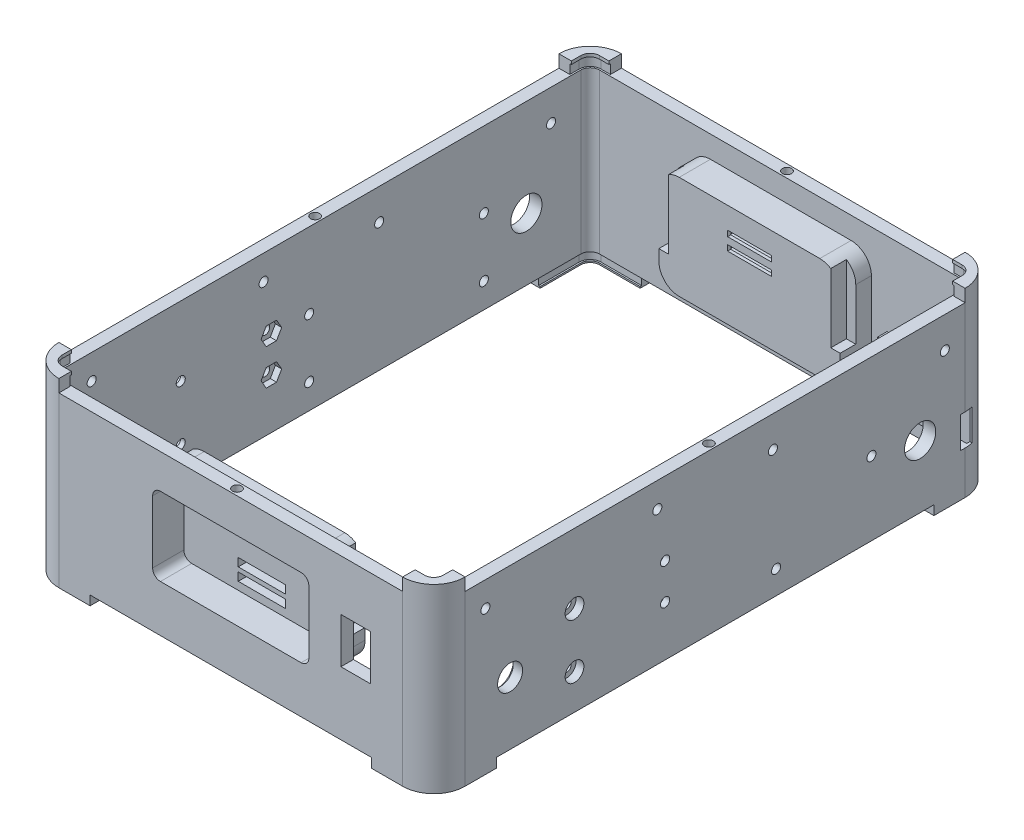
SolidWorks part; units mm, degrees
ref_plane "Спереди" through (0, 0, 0) normal (0, 0, 1) x (1, 0, 0)
ref_plane "Сверху" through (0, 0, 0) normal (0, 1, 0) x (1, 0, 0)
ref_plane "Справа" through (0, 0, 0) normal (1, 0, 0) x (0, 0, -1)
sketch "Эскиз1" plane through (0, 0, 0) normal (0, 1, 0) x (1, 0, 0)
  line L1 (-65, -90) -> (65, -90)
  line L2 (-65, -90) -> (-65, 90)
  line L3 (-65, 90) -> (65, 90)
  line L4 (65, -90) -> (65, 90)
  line L5 (-65, -90) -> (65, 90) construction
  line L6 (-65, 90) -> (65, -90) construction
  point P0 (0, 0)
  dimension "D1" = 130
  dimension "D2" = 180
extrude "Бобышка-Вытянуть1" add sketch "Эскиз1" along normal blind 55
sketch "Эскиз2" plane through (0, 0, 90) normal (0, 0, 1) x (1, 0, 0)
  line L0 (-1050, 27.5) -> (48950, 27.5) construction
  line L1 (-65, 55) -> (-65, 0) construction
  line L2 (0, -999.2777) -> (0, 49000.7223) construction
  line L4 (-22.5, 15) -> (22.5, 15)
  line L5 (-25, 17.5) -> (-25, 37.5)
  line L6 (-22.5, 40) -> (22.5, 40)
  line L7 (25, 17.5) -> (25, 37.5)
  line L8 (-25, 15) -> (25, 40) construction
  line L9 (-25, 40) -> (25, 15) construction
  arc A0 (-22.5, 40) -> (-25, 37.5) centre (-22.5, 37.5) ccw
  arc A1 (-25, 17.5) -> (-22.5, 15) centre (-22.5, 17.5) ccw
  arc A2 (25, 17.5) -> (22.5, 15) centre (22.5, 17.5) cw
  arc A3 (25, 37.5) -> (22.5, 40) centre (22.5, 37.5) ccw
  point P5 (-65, 27.5)
  point P6 (0, 27.5)
  dimension "D3" = 2.5
  dimension "D4" = 2.5
  dimension "D1" = 25
  dimension "D2" = 50
extrude "Вырез-Вытянуть1" cut sketch "Эскиз2" against normal blind 10
sketch "Эскиз4" plane through (0, 55, 0) normal (0, 1, 0) x (1, 0, 0)
  line L0 (0, -1000) -> (0, 49000) construction
  line L1 (-1000, 0) -> (49000, 0) construction
  line L2 (-22.5, 41.5) -> (22.5, 41.5)
  line L3 (-25, 44) -> (-25, 64)
  line L4 (-22.5, 66.5) -> (22.5, 66.5)
  line L5 (-22.5, -12.5) -> (22.5, -12.5)
  line L6 (-25, -10) -> (-25, 10)
  line L7 (-22.5, 12.5) -> (22.5, 12.5)
  line L8 (25, -10) -> (25, 10)
  line L9 (-25, -12.5) -> (25, 12.5) construction
  line L10 (-25, 12.5) -> (25, -12.5) construction
  line L11 (25, 44) -> (25, 64)
  line L12 (-25, 41.5) -> (25, 66.5) construction
  line L13 (-25, 66.5) -> (25, 41.5) construction
  line L14 (-25, -12.5) -> (25, -12.5) [skipped]
  line L15 (-25, -12.5) -> (-25, 12.5) [skipped]
  line L16 (-25, 12.5) -> (25, 12.5) [skipped]
  line L17 (25, -12.5) -> (25, 12.5) [skipped]
  line L18 (-25, -12.5) -> (25, 12.5) construction
  line L19 (-25, 12.5) -> (25, -12.5) construction
  line L20 (-22.5, -66.5) -> (22.5, -66.5)
  line L21 (-25, -64) -> (-25, -44)
  line L22 (-22.5, -41.5) -> (22.5, -41.5)
  line L23 (25, -64) -> (25, -44)
  line L24 (-25, -66.5) -> (25, -41.5) construction
  line L25 (-25, -41.5) -> (25, -66.5) construction
  arc A0 (22.5, -41.5) -> (25, -44) centre (22.5, -44) cw
  arc A1 (25, -64) -> (22.5, -66.5) centre (22.5, -64) cw
  arc A2 (-22.5, -66.5) -> (-25, -64) centre (-22.5, -64) cw
  arc A3 (-25, -44) -> (-22.5, -41.5) centre (-22.5, -44) cw
  arc A4 (-25, 64) -> (-22.5, 66.5) centre (-22.5, 64) cw
  arc A5 (-22.5, 12.5) -> (-25, 10) centre (-22.5, 10) ccw
  arc A6 (25, -10) -> (22.5, -12.5) centre (22.5, -10) cw
  arc A7 (22.5, 66.5) -> (25, 64) centre (22.5, 64) cw
  arc A8 (25, 44) -> (22.5, 41.5) centre (22.5, 44) cw
  arc A9 (-22.5, 41.5) -> (-25, 44) centre (-22.5, 44) cw
  arc A10 (22.5, 12.5) -> (25, 10) centre (22.5, 10) cw
  arc A11 (-22.5, -12.5) -> (-25, -10) centre (-22.5, -10) cw
  point P8 (0, 0)
  point P9 (0, 54)
  point P18 (0, 0)
  point P23 (0, -54)
  dimension "D7" = 2.5
  dimension "D8" = 2.5
  dimension "D1" = 25
  dimension "D2" = 50
  dimension "D5" = 41.5
  dimension "D6" = 41.5
  dimension "D3" = 2
  dimension "D4" = 2
extrude "Вырез-Вытянуть2" cut sketch "Эскиз4" against normal blind 10
mirror "Зеркальное отражение1" about plane through (0, 0, 0) normal (0, 0, 1) of "Вырез-Вытянуть1"
shell "Оболочка1" thickness 4 removed face at (0, 0, 0)
sketch "Эскиз5" plane through (-65, 0, 0) normal (-1, 0, 0) x (0, 0, 1)
  line L0 (45, 28.75) -> (45, 11.25) construction
  line L2 (90, 55) -> (90, 0) construction
  line L4 (-90, 0) -> (90, 0) construction
  line L7 (-1075, 20) -> (48925, 20) construction
  line L8 (-90, 55) -> (-90, 0) construction
  circle A3 centre (45, 28.75) radius 1.45
  circle A4 centre (45, 11.25) radius 1.45
  circle A5 centre (65.6, 20) radius 4
  circle A6 centre (-65.6, 20) radius 5
  dimension "D2" = 17.5
  dimension "D3" = 20
  dimension "D6" = 10
  dimension "D1" = 17.5
  dimension "D5" = 2.9
  dimension "D9" = 45
  dimension "D10" = 20.6
  dimension "D11" = 8
  dimension "D4" = 24.4
extrude "Вырез-Вытянуть3" cut sketch "Эскиз5" against normal blind 15
sketch "Эскиз6" plane through (-65, 0, 0) normal (-1, 0, 0) x (0, 0, 1)
  circle A2 centre (45, 28.75) radius 3
  circle A3 centre (45, 11.25) radius 3
  dimension "D1" = 6
extrude "Вырез-Вытянуть4" cut sketch "Эскиз6" against normal blind 2.5
sketch "Эскиз11" plane through (-61, 0, 0) normal (1, 0, 0) x (0, 0, -1)
  circle A1 centre (-65.6, 20) radius 5
  dimension "D1" = 10
extrude "Вырез-Вытянуть16" cut sketch "Эскиз11" against normal blind 1
mirror "Зеркальное отражение2" about plane through (0, 0, 0) normal (1, 0, 0) of "Вырез-Вытянуть3", "Вырез-Вытянуть4", "Вырез-Вытянуть16"
sketch "Эскиз12" plane through (0, 11, 0) normal (0, -1, 0) x (-1, 0, 0)
  line L0 (-1014.7864, -78) -> (48985.2136, -78) construction
  line L1 (22.5, -76) -> (-22.5, -76) construction
  line L2 (0, -1061) -> (0, 48939) construction
  line L3 (-10, -1061) -> (-10, 48939) construction
  line L4 (10, -1061) -> (10, 48939) construction
  circle A0 centre (-10, -78) radius 1.45
  circle A1 centre (10, -78) radius 1.45
  point P7 (0, -76)
  dimension "D4" = 2.9
  dimension "D1" = 2
  dimension "D2" = 20
  dimension "D3" = 10
extrude "Вырез-Вытянуть17" cut sketch "Эскиз12" against normal blind 14
sketch "Эскиз15" plane through (0, 45, 0) normal (0, 1, 0) x (1, 0, 0)
  line L0 (-1010.1672, -62.5) -> (48989.8328, -62.5) construction
  line L1 (0, -1031.5) -> (0, 48968.5) construction
  line L2 (-7.6, -63.8) -> (7.6, -63.8)
  line L3 (-7.6, -63.8) -> (-7.6, -61.2)
  line L4 (-7.6, -61.2) -> (7.6, -61.2)
  line L5 (7.6, -63.8) -> (7.6, -61.2)
  line L6 (-7.6, -63.8) -> (7.6, -61.2) construction
  line L7 (-7.6, -61.2) -> (7.6, -63.8) construction
  line L8 (22.5, -41.5) -> (-22.5, -41.5) construction
  line L9 (-22.5, -66.5) -> (22.5, -66.5) construction
  line L10 (-7.6, -9.8) -> (7.6, -9.8)
  line L11 (-7.6, -9.8) -> (-7.6, -7.2)
  line L12 (-7.6, -7.2) -> (7.6, -7.2)
  line L13 (7.6, -9.8) -> (7.6, -7.2)
  line L14 (-7.6, -9.8) -> (7.6, -7.2) construction
  line L15 (-7.6, -7.2) -> (7.6, -9.8) construction
  line L16 (-7.6, 44.2) -> (7.6, 44.2)
  line L17 (-7.6, 44.2) -> (-7.6, 46.8)
  line L18 (-7.6, 46.8) -> (7.6, 46.8)
  line L19 (7.6, 44.2) -> (7.6, 46.8)
  line L20 (-7.6, 44.2) -> (7.6, 46.8) construction
  line L21 (-7.6, 46.8) -> (7.6, 44.2) construction
  line L23 (22.5, 12.5) -> (-22.5, 12.5) construction
  line L24 (-7.6, -59.8) -> (7.6, -59.8)
  line L25 (-7.6, -59.8) -> (-7.6, -57.2)
  line L26 (-7.6, -57.2) -> (7.6, -57.2)
  line L27 (7.6, -59.8) -> (7.6, -57.2)
  line L28 (-7.6, -59.8) -> (7.6, -57.2) construction
  line L29 (-7.6, -57.2) -> (7.6, -59.8) construction
  line L30 (-7.6, -5.8) -> (7.6, -5.8)
  line L31 (-7.6, -5.8) -> (-7.6, -3.2)
  line L32 (-7.6, -3.2) -> (7.6, -3.2)
  line L33 (7.6, -5.8) -> (7.6, -3.2)
  line L34 (-7.6, -5.8) -> (7.6, -3.2) construction
  line L35 (-7.6, -3.2) -> (7.6, -5.8) construction
  line L36 (-7.6, 48.2) -> (7.6, 48.2)
  line L37 (-7.6, 48.2) -> (-7.6, 50.8)
  line L38 (-7.6, 50.8) -> (7.6, 50.8)
  line L39 (7.6, 48.2) -> (7.6, 50.8)
  line L40 (-7.6, 48.2) -> (7.6, 50.8) construction
  line L41 (-7.6, 50.8) -> (7.6, 48.2) construction
  line L42 (-22.5, -12.5) -> (22.5, -12.5) construction
  circle A0 centre (-20, -46.5) radius 2.5
  circle A1 centre (20, -46.5) radius 2.5
  circle A2 centre (-20, 7.5) radius 2.5
  circle A3 centre (20, 7.5) radius 2.5
  circle A4 centre (-20, 61.5) radius 2.5
  circle A5 centre (20, 61.5) radius 2.5
  point P1 (0, -62.5)
  point P12 (0, -41.5)
  point P16 (0, -8.5)
  point P21 (0, 45.5)
  point P41 (0, -4.5)
  point P42 (0, -58.5)
  point P51 (0, 49.5)
  dimension "D6" = 40
  dimension "D8" = 5
  dimension "D1" = 2.6
  dimension "D2" = 15.2
  dimension "D3" = 4
  dimension "D4" = 3
  dimension "D5" = 4
  dimension "D7" = 40
  dimension "D9" = 5
  dimension "D10" = 3
  dimension "D11" = 5
  dimension "D13" = 4
  dimension "D15" = 4
  dimension "D12" = 2
  dimension "D14" = 3
extrude "Вырез-Вытянуть20" cut sketch "Эскиз15" against normal blind 3
sketch "Эскиз16" plane through (0, 42, 0) normal (0, 1, 0) x (1, 0, 0)
  line L0 (-7.6, -62.5) -> (7.6, -62.5) construction
  line L1 (-7.6, -61.2) -> (-7.6, -63.8) construction
  line L2 (7.6, -63.8) -> (7.6, -61.2) construction
  line L3 (0, -1000) -> (0, 49000) construction
  line L4 (-7, -63.4) -> (7, -63.4)
  line L5 (-7, -63.4) -> (-7, -61.6)
  line L6 (-7, -61.6) -> (7, -61.6)
  line L7 (7, -63.4) -> (7, -61.6)
  line L8 (-7, -63.4) -> (7, -61.6) construction
  line L9 (-7, -61.6) -> (7, -63.4) construction
  line L10 (-7, -9.4) -> (7, -9.4)
  line L11 (-7, -9.4) -> (-7, -7.6)
  line L12 (-7, -7.6) -> (7, -7.6)
  line L13 (7, -9.4) -> (7, -7.6)
  line L14 (-7.6, -8.5) -> (7.6, -8.5) construction
  line L15 (-7, -9.4) -> (7, -7.6) construction
  line L16 (-7, -7.6) -> (7, -9.4) construction
  line L17 (-7, 44.6) -> (7, 44.6)
  line L18 (-7, 44.6) -> (-7, 46.4)
  line L19 (-7, 46.4) -> (7, 46.4)
  line L20 (7, 44.6) -> (7, 46.4)
  line L21 (-7.6, 45.5) -> (7.6, 45.5) construction
  line L22 (-7, 44.6) -> (7, 46.4) construction
  line L23 (-7, 46.4) -> (7, 44.6) construction
  line L24 (-7.6, -7.2) -> (-7.6, -9.8) construction
  line L25 (-7.6, -58.5) -> (7.6, -58.5) construction
  line L26 (-7, -59.4) -> (7, -59.4)
  line L27 (-7, -59.4) -> (-7, -57.6)
  line L28 (-7, -57.6) -> (7, -57.6)
  line L29 (7, -59.4) -> (7, -57.6)
  line L30 (-7, -59.4) -> (7, -57.6) construction
  line L31 (-7, -57.6) -> (7, -59.4) construction
  line L32 (-7.6, -57.2) -> (-7.6, -59.8) construction
  line L33 (7.6, -59.8) -> (7.6, -57.2) construction
  line L34 (-7.6, -4.5) -> (7.6, -4.5) construction
  line L35 (-7.6, -3.2) -> (-7.6, -5.8) construction
  line L36 (7.6, -5.8) -> (7.6, -3.2) construction
  line L37 (-7.6, -9.8) -> (7.6, -9.8) construction
  line L38 (-7, -5.4) -> (7, -5.4)
  line L39 (-7, -5.4) -> (-7, -3.6)
  line L40 (-7, -3.6) -> (7, -3.6)
  line L41 (7, -5.4) -> (7, -3.6)
  line L42 (-7, -5.4) -> (7, -3.6) construction
  line L43 (-7, -3.6) -> (7, -5.4) construction
  line L44 (7.6, -9.8) -> (7.6, -7.2) construction
  line L45 (-7.6, 46.8) -> (-7.6, 44.2) construction
  line L46 (7.6, 44.2) -> (7.6, 46.8) construction
  line L47 (-7.6, 44.2) -> (7.6, 44.2) construction
  line L48 (-7.6, 49.5) -> (7.6, 49.5) construction
  line L49 (-7.6, 50.8) -> (-7.6, 48.2) construction
  line L50 (7.6, 48.2) -> (7.6, 50.8) construction
  line L52 (-7, 48.6) -> (7, 48.6)
  line L53 (-7, 48.6) -> (-7, 50.4)
  line L54 (-7, 50.4) -> (7, 50.4)
  line L55 (7, 48.6) -> (7, 50.4)
  line L56 (-7, 48.6) -> (7, 50.4) construction
  line L57 (-7, 50.4) -> (7, 48.6) construction
  point P6 (0, -62.5)
  point P12 (0, -58.5)
  point P17 (0, -8.5)
  point P24 (0, 36.6)
  point P41 (0, -4.5)
  point P54 (0, 49.5)
  dimension "D1" = 1.8
  dimension "D2" = 14
  dimension "D4" = 0.4
  dimension "D3" = 0.4
extrude "Вырез-Вытянуть21" cut sketch "Эскиз16" against normal blind 3
sketch "Эскиз17" plane through (0, 0, 80) normal (0, 0, 1) x (1, 0, 0)
  line L0 (-7.6, 17.5) -> (7.6, 17.5)
  line L1 (-7.6, 17.5) -> (-7.6, 20.1)
  line L2 (-7.6, 20.1) -> (7.6, 20.1)
  line L3 (7.6, 17.5) -> (7.6, 20.1)
  line L4 (-7.6, 17.5) -> (7.6, 20.1) construction
  line L5 (-7.6, 20.1) -> (7.6, 17.5) construction
  line L7 (-7.6, 21.5) -> (7.6, 21.5)
  line L8 (-22.5, 15) -> (22.5, 15) construction
  line L9 (0, -965) -> (0, 49035) construction
  line L10 (22.5, 40) -> (-22.5, 40) construction
  line L11 (-7.6, 21.5) -> (-7.6, 24.1)
  line L12 (-7.6, 24.1) -> (7.6, 24.1)
  line L13 (7.6, 21.5) -> (7.6, 24.1)
  line L14 (-7.6, 21.5) -> (7.6, 24.1) construction
  line L15 (-7.6, 24.1) -> (7.6, 21.5) construction
  circle A0 centre (-20, 35) radius 2.5
  circle A1 centre (20, 35) radius 2.5
  point P0 (0, 18.8)
  point P11 (0, 22.8)
  point P20 (0, 40)
  dimension "D5" = 5
  dimension "D8" = 4
  dimension "D1" = 2.6
  dimension "D2" = 15.2
  dimension "D3" = 40
  dimension "D4" = 40
  dimension "D6" = 2.5
  dimension "D7" = 5
extrude "Вырез-Вытянуть22" cut sketch "Эскиз17" against normal blind 3
sketch "Эскиз18" plane through (0, 0, 77) normal (0, 0, 1) x (1, 0, 0)
  line L0 (-7.6, 18.8) -> (7.6, 18.8) construction
  line L1 (-7.6, 20.1) -> (-7.6, 17.5) construction
  line L2 (7.6, 17.5) -> (7.6, 20.1) construction
  line L3 (0, -980.9) -> (0, 49019.1) construction
  line L4 (-7, 17.9) -> (7, 17.9)
  line L5 (-7, 17.9) -> (-7, 19.7)
  line L6 (-7, 19.7) -> (7, 19.7)
  line L7 (7, 17.9) -> (7, 19.7)
  line L8 (-7, 17.9) -> (7, 19.7) construction
  line L9 (-7, 19.7) -> (7, 17.9) construction
  line L10 (7.6, 24.1) -> (-7.6, 24.1) construction
  line L12 (-7, 21.9) -> (7, 21.9)
  line L13 (-7, 21.9) -> (-7, 23.7)
  line L14 (-7, 23.7) -> (7, 23.7)
  line L15 (7, 21.9) -> (7, 23.7)
  line L16 (-7, 21.9) -> (7, 23.7) construction
  line L17 (-7, 23.7) -> (7, 21.9) construction
  point P6 (0, 18.8)
  point P12 (0, 22.8)
  point P16 (0, 24.1)
  dimension "D1" = 1.8
  dimension "D2" = 14
  dimension "D3" = 4
extrude "Вырез-Вытянуть23" cut sketch "Эскиз18" against normal blind 3
sketch "Эскиз19" plane through (0, 0, -80) normal (0, 0, -1) x (1, 0, 0)
  line L0 (-7.6, -37.5) -> (7.6, -37.5)
  line L1 (-7.6, -37.5) -> (-7.6, -34.9)
  line L2 (-7.6, -34.9) -> (7.6, -34.9)
  line L3 (7.6, -37.5) -> (7.6, -34.9)
  line L4 (-7.6, -37.5) -> (7.6, -34.9) construction
  line L5 (-7.6, -34.9) -> (7.6, -37.5) construction
  line L6 (0, -1010) -> (0, 48990) construction
  line L7 (-22.5, -15) -> (22.5, -15) construction
  line L9 (-7.6, -33.5) -> (7.6, -33.5)
  line L10 (22.5, -40) -> (-22.5, -40) construction
  line L11 (-7.6, -33.5) -> (-7.6, -30.9)
  line L12 (-7.6, -30.9) -> (7.6, -30.9)
  line L13 (7.6, -33.5) -> (7.6, -30.9)
  line L14 (-7.6, -33.5) -> (7.6, -30.9) construction
  line L15 (-7.6, -30.9) -> (7.6, -33.5) construction
  circle A0 centre (-20, -20) radius 2.5
  circle A1 centre (20, -20) radius 2.5
  point P0 (0, -36.2)
  point P14 (0, -15)
  point P16 (0, -32.2)
  dimension "D5" = 5
  dimension "D7" = 2.5
  dimension "D1" = 2.6
  dimension "D2" = 15.2
  dimension "D3" = 40
  dimension "D4" = 40
  dimension "D6" = 5
  dimension "D8" = 4
extrude "Вырез-Вытянуть24" cut sketch "Эскиз19" against normal blind 3
sketch "Эскиз20" plane through (0, 0, -77) normal (0, 0, -1) x (1, 0, 0)
  line L0 (-1007.6, -36.2) -> (48992.4, -36.2) construction
  line L1 (-7.6, -34.9) -> (-7.6, -37.5) construction
  line L3 (-7, -37.1) -> (7, -37.1)
  line L4 (-7, -37.1) -> (-7, -35.3)
  line L5 (-7, -35.3) -> (7, -35.3)
  line L6 (7, -37.1) -> (7, -35.3)
  line L7 (-7, -37.1) -> (7, -35.3) construction
  line L8 (-7, -35.3) -> (7, -37.1) construction
  line L9 (-7, -31.3) -> (7, -31.3)
  line L10 (0, -1029.9) -> (0, 48970.1) construction
  line L11 (7.6, -34.9) -> (-7.6, -34.9) construction
  line L12 (-7, -31.3) -> (-7, -33.1)
  line L13 (-7, -33.1) -> (7, -33.1)
  line L14 (7, -31.3) -> (7, -33.1)
  line L15 (-7, -31.3) -> (7, -33.1) construction
  line L16 (-7, -33.1) -> (7, -31.3) construction
  point P1 (0, -36.2)
  point P5 (-7.6, -36.2)
  point P10 (0, -32.2)
  point P18 (0, -34.9)
  dimension "D1" = 1.8
  dimension "D2" = 14
  dimension "D3" = 4
extrude "Вырез-Вытянуть25" cut sketch "Эскиз20" against normal blind 5
sketch "Эскиз21" plane through (0, 0, 90) normal (0, 0, -1) x (1, 0, 0)
  line L0 (-975, -27.5) -> (49025, -27.5) construction
  line L1 (35.25, -34.75) -> (44.75, -34.75)
  line L2 (35.25, -34.75) -> (35.25, -20.25)
  line L3 (35.25, -20.25) -> (44.75, -20.25)
  line L4 (44.75, -34.75) -> (44.75, -20.25)
  line L5 (35.25, -34.75) -> (44.75, -20.25) construction
  line L6 (35.25, -20.25) -> (44.75, -34.75) construction
  line L7 (25, -17.5) -> (25, -37.5) construction
  line L8 (40, -1022.5) -> (40, 48977.5) construction
  line L9 (65, -55) -> (65, 0) construction
  point P0 (40, -27.5)
  point P10 (25, -27.5)
  dimension "D1" = 9.5
  dimension "D2" = 14.5
  dimension "D3" = 25
extrude "Вырез-Вытянуть26" cut sketch "Эскиз21" along normal blind 4
sketch "Эскиз22" plane through (0, 0, 0) normal (0, -1, 0) x (-1, 0, 0)
  line L0 (-63, -925) -> (-63, 49075) construction
  line L2 (-65, -90) -> (-65, 90) construction
  line L3 (-1046.2998, 88) -> (48953.7002, 88) construction
  line L4 (-65, 90) -> (65, 90) construction
  line L5 (63, -925) -> (63, 49075) construction
  line L6 (65, 90) -> (65, -90) construction
  line L7 (-1052.5, -88) -> (48947.5, -88) construction
  line L8 (65, -90) -> (-65, -90) construction
  line L9 (0, -925) -> (0, 49075) construction
  line L10 (-1052.5, 0) -> (48947.5, 0) construction
  circle A4 centre (0, 88) radius 1.425
  circle A5 centre (0, -88) radius 1.425
  circle A6 centre (-63, 0) radius 1.425
  circle A7 centre (63, 0) radius 1.425
  point P27 (0, 90)
  point P34 (-65, 0)
  dimension "D5" = 2.85
  dimension "D1" = 2
  dimension "D2" = 2
  dimension "D3" = 2
  dimension "D4" = 2
extrude "Вырез-Вытянуть27" cut sketch "Эскиз22" against normal blind 9
sketch "Эскиз24" plane through (-65, 0, 0) normal (-1, 0, 0) x (0, 0, 1)
  line L0 (0, -1000) -> (0, 49000) construction
  line L1 (16, -988.2808) -> (16, 49011.7192) construction
  line L2 (-90, 0) -> (90, 0) construction
  circle A0 centre (16, 16) radius 1.475
  circle A1 centre (16, 27.5) radius 1.475
  dimension "D4" = 2.95
  dimension "D1" = 11.5
  dimension "D2" = 16
  dimension "D3" = 16
extrude "Вырез-Вытянуть28" cut sketch "Эскиз24" against normal through all
fillet "Скругление1" radius 10 4 edges at (65, 27.5, -90) (-65, 27.5, -90) (65, 27.5, 90) (-65, 27.5, 90)
sketch "Эскиз26" plane through (61, 0, 0) normal (-1, 0, 0) x (0, 0, 1)
  line L1 (17.6454, 18.85) -> (14.3546, 18.85)
  line L2 (14.3546, 18.85) -> (12.7091, 16)
  line L3 (12.7091, 16) -> (14.3546, 13.15)
  line L4 (14.3546, 13.15) -> (17.6454, 13.15)
  line L5 (17.6454, 13.15) -> (19.2909, 16)
  line L6 (19.2909, 16) -> (17.6454, 18.85)
  line L7 (17.6454, 30.35) -> (14.3546, 30.35)
  line L8 (14.3546, 30.35) -> (12.7091, 27.5)
  line L9 (12.7091, 27.5) -> (14.3546, 24.65)
  line L10 (14.3546, 24.65) -> (17.6454, 24.65)
  line L11 (17.6454, 24.65) -> (19.2909, 27.5)
  line L12 (19.2909, 27.5) -> (17.6454, 30.35)
  circle A0 centre (16, 16) radius 2.85 construction
  circle A1 centre (16, 27.5) radius 2.85 construction
  dimension "D1" = 5.7
extrude "Вырез-Вытянуть29" cut sketch "Эскиз26" against normal blind 2 and the other way blind 124
fillet "Скругление2" radius 3 4 edges at (61, 25.5, 86) (61, 25.5, -86) (-61, 25.5, -86) (-61, 25.5, 86)
sketch "Эскиз27" plane through (0, 0, 0) normal (0, -1, 0) x (1, 0, 0)
  line L0 (-55, -90) -> (-45, -90)
  line L1 (55, -90) -> (-55, -90) construction
  line L2 (-45, -90) -> (-45, -86)
  line L3 (58, -86) -> (-58, -86) construction
  line L4 (-45, -86) -> (-58, -86)
  line L6 (-61, -83) -> (-61, -70)
  line L7 (-61, -83) -> (-61, 83) construction
  line L8 (-61, -70) -> (-65, -70)
  line L9 (-65, -80) -> (-65, 80) construction
  line L10 (-65, -70) -> (-65, -80)
  line L11 (0, -1000) -> (0, 49000) construction
  line L12 (-1000, 0) -> (49000, 0) construction
  line L13 (65, -70) -> (65, -80)
  line L14 (61, -70) -> (65, -70)
  line L15 (61, -83) -> (61, -70)
  line L16 (45, -86) -> (58, -86)
  line L17 (45, -90) -> (45, -86)
  line L18 (55, -90) -> (45, -90)
  line L19 (55, 90) -> (45, 90)
  line L20 (45, 90) -> (45, 86)
  line L21 (45, 86) -> (58, 86)
  line L22 (61, 83) -> (61, 70)
  line L23 (61, 70) -> (65, 70)
  line L24 (65, 70) -> (65, 80)
  line L25 (-65, 70) -> (-65, 80)
  line L26 (-61, 70) -> (-65, 70)
  line L27 (-61, 83) -> (-61, 70)
  line L28 (-45, 86) -> (-58, 86)
  line L29 (-45, 90) -> (-45, 86)
  line L30 (-55, 90) -> (-45, 90)
  arc A1 (-65, -80) -> (-55, -90) centre (-55, -80) ccw construction
  arc A4 (61, -83) -> (58, -86) centre (58, -83) cw
  arc A5 (-65, -80) -> (-55, -90) centre (-55, -80) ccw
  arc A6 (65, -80) -> (55, -90) centre (55, -80) cw
  arc A7 (-61, 83) -> (-58, 86) centre (-58, 83) cw
  arc A8 (-61, -83) -> (-58, -86) centre (-58, -83) ccw construction
  arc A9 (-61, -83) -> (-58, -86) centre (-58, -83) ccw
  arc A10 (65, 80) -> (55, 90) centre (55, 80) ccw
  arc A11 (-65, 80) -> (-55, 90) centre (-55, 80) cw
  arc A12 (61, 83) -> (58, 86) centre (58, 83) ccw
  dimension "D1" = 10
extrude "Бобышка-Вытянуть2" add sketch "Эскиз27" along normal blind 3
sketch "Эскиз28" plane through (0, 0, 0) normal (0, -1, 0) x (1, 0, 0)
  line L0 (-61, 70) -> (-61, 83) construction
  line L2 (-61, 70) -> (-61, 83)
  line L3 (-58, 86) -> (-45, 86)
  line L4 (-45, 86) -> (-45, 86.5)
  line L5 (-45, 86) -> (-45, 90) construction
  line L6 (-45, 86.5) -> (-58, 86.5)
  line L7 (-1000, 0) -> (49000, 0) construction
  line L8 (-61.5, 83) -> (-61.5, 70)
  line L9 (-65, 70) -> (-61, 70) construction
  line L10 (-61.5, 70) -> (-61, 70)
  line L11 (0, -1000) -> (0, 49000) construction
  line L12 (61.5, 70) -> (61, 70)
  line L13 (61.5, 83) -> (61.5, 70)
  line L14 (45, 86.5) -> (58, 86.5)
  line L15 (45, 86) -> (45, 86.5)
  line L16 (58, 86) -> (45, 86)
  line L17 (61, 70) -> (61, 83)
  line L18 (61, -70) -> (61, -83)
  line L19 (58, -86) -> (45, -86)
  line L20 (45, -86) -> (45, -86.5)
  line L21 (45, -86.5) -> (58, -86.5)
  line L22 (61.5, -83) -> (61.5, -70)
  line L23 (61.5, -70) -> (61, -70)
  line L24 (-61.5, -70) -> (-61, -70)
  line L25 (-61.5, -83) -> (-61.5, -70)
  line L26 (-45, -86.5) -> (-58, -86.5)
  line L27 (-45, -86) -> (-45, -86.5)
  line L28 (-58, -86) -> (-45, -86)
  line L29 (-61, -70) -> (-61, -83)
  arc A0 (-58, 86) -> (-61, 83) centre (-58, 83) ccw construction
  arc A1 (-58, 86) -> (-61, 83) centre (-58, 83) ccw
  arc A2 (-61.5, 83) -> (-58, 86.5) centre (-58, 83) cw
  arc A3 (61.5, 83) -> (58, 86.5) centre (58, 83) ccw
  arc A4 (58, 86) -> (61, 83) centre (58, 83) cw
  arc A5 (58, -86) -> (61, -83) centre (58, -83) ccw
  arc A6 (61.5, -83) -> (58, -86.5) centre (58, -83) cw
  arc A7 (-61.5, -83) -> (-58, -86.5) centre (-58, -83) ccw
  arc A8 (-58, -86) -> (-61, -83) centre (-58, -83) cw
  dimension "D1" = 0.5
extrude "Вырез-Вытянуть30" cut sketch "Эскиз28" along normal blind 2.5
sketch "Эскиз30" plane through (0, 51, 0) normal (0, -1, 0) x (1, 0, 0)
  line L0 (-29, -10) -> (-29, 10) construction
  line L1 (-58.5, 86) -> (-29, 86)
  line L2 (-61, 83.5) -> (-61, 6)
  line L3 (-61, 6) -> (-29, 6)
  line L4 (-29, 86) -> (-29, 6)
  line L5 (-58, 86) -> (58, 86) construction
  line L6 (-61, -83) -> (-61, 83) construction
  line L7 (0, -1000) -> (0, 49000) construction
  line L8 (29, 86) -> (29, 6)
  line L9 (61, 6) -> (29, 6)
  line L10 (61, 83.5) -> (61, 6)
  line L11 (58.5, 86) -> (29, 86)
  arc A0 (-58.5, 86) -> (-61, 83.5) centre (-58.5, 83.5) ccw
  arc A1 (58.5, 86) -> (61, 83.5) centre (58.5, 83.5) cw
  dimension "D1" = 2.5
  dimension "D2" = 80
extrude "Вырез-Вытянуть32" cut sketch "Эскиз30" against normal blind 2
sketch "Эскиз29" plane through (-61, 0, 0) normal (1, 0, 0) x (0, 0, -1)
  line L1 (83, 51) -> (-6, 51) construction
  line L2 (-86, 0) -> (-86, 51) construction
  line L3 (0, -1000) -> (0, 49000) construction
  line L4 (90, 55) -> (90, -3) construction
  line L6 (-80, 55) -> (80, 55) construction
  circle A0 centre (-73.5, 43) radius 1.45
  circle A1 centre (-18.5, 43) radius 1.45
  circle A4 centre (18.5, 41) radius 1.45
  circle A5 centre (73.5, 41) radius 1.45
  dimension "D1" = 8
  dimension "D4" = 2.9
  dimension "D5" = 55
  dimension "D2" = 12.5
  dimension "D3" = 55
  dimension "D6" = 16.5
  dimension "D7" = 14
extrude "Вырез-Вытянуть31" cut sketch "Эскиз29" against normal through all both and the other way through all
sketch "Эскиз31" plane through (0, 41, 0) normal (0, -1, 0) x (1, 0, 0)
  line L0 (26, -1043.9084) -> (26, 48956.0916) construction
  line L2 (29, 64) -> (29, 44) construction
  line L3 (29, -76) -> (29, -86) construction
  line L4 (26, 81) -> (29, 81)
  line L5 (26, 81) -> (26, -81)
  line L6 (26, -81) -> (29, -81)
  line L7 (29, 81) -> (29, -81)
  line L8 (22.5, 76) -> (22.5, 86) construction
  line L9 (-977.5, 81) -> (49022.5, 81) construction
  line L10 (0, -1000) -> (0, 49000) construction
  line L11 (-26, -1043.9084) -> (-26, 48956.0916) construction
  line L12 (-29, 81) -> (-29, -81)
  line L13 (-26, -81) -> (-29, -81)
  line L14 (-26, 81) -> (-26, -81)
  line L15 (-26, 81) -> (-29, 81)
  point P16 (22.5, 81)
  dimension "D1" = 3
extrude "Вырез-Вытянуть33" cut sketch "Эскиз31" against normal up to surface (10 mm away) and the other way blind 20 up to face at (0, 51, 27)
sketch "Эскиз32" plane through (61, 0, 0) normal (-1, 0, 0) x (0, 0, 1)
  line L0 (-83, 51) -> (-83, 0) construction
  line L1 (-83, 7) -> (-81.5, 7)
  line L2 (-83, 7) -> (-83, 24.5)
  line L3 (-83, 24.5) -> (-81.5, 24.5)
  line L4 (-81.5, 7) -> (-81.5, 24.5)
  line L5 (83, 0) -> (-83, 0) construction
  dimension "D1" = 17.5
  dimension "D2" = 1.5
  dimension "D3" = 7
extrude "Вырез-Вытянуть34" cut sketch "Эскиз32" against normal blind 3 contours L1 L4 L3 L2
sketch "Эскиз33" plane through (61, 0, 0) normal (-1, 0, 0) x (0, 0, 1)
  line L0 (-81.5, 7) -> (-81.5, 24.5) construction
  line L1 (-82.5, 20.75) -> (-78.5, 20.75)
  line L2 (-82.5, 20.75) -> (-82.5, 10.75)
  line L3 (-82.5, 10.75) -> (-78.5, 10.75)
  line L4 (-78.5, 20.75) -> (-78.5, 10.75)
  line L5 (-1081.5, 15.75) -> (48918.5, 15.75) construction
  point P7 (-78.5, 15.75)
  point P9 (-81.5, 15.75)
  dimension "D1" = 10
  dimension "D2" = 4
  dimension "D3" = 3
extrude "Вырез-Вытянуть35" cut sketch "Эскиз33" against normal blind 4
sketch "Эскиз34" plane through (0, 0, -86) normal (0, 0, 1) x (1, 0, 0)
  line L0 (61, 51) -> (61, 24.5) construction
  line L1 (34, 7) -> (61, 7)
  line L2 (34, 7) -> (34, 24.5)
  line L3 (34, 24.5) -> (61, 24.5)
  line L4 (61, 7) -> (61, 24.5)
  line L5 (58, 0) -> (-58, 0) construction
  dimension "D1" = 7
  dimension "D2" = 27
  dimension "D3" = 17.5
extrude "Бобышка-Вытянуть3" add sketch "Эскиз34" along normal blind 3
sketch "Эскиз35" plane through (61, 0, 0) normal (-1, 0, 0) x (0, 0, 1)
  line L0 (-90, 55) -> (-90, -3) construction
  line L1 (83, 0) -> (-83, 0) construction
  circle A0 centre (-50, 23.5) radius 1.45
  circle A1 centre (-19.5, 7.5) radius 1.45
  dimension "D1" = 16
  dimension "D5" = 2.9
  dimension "D2" = 30.5
  dimension "D3" = 40
  dimension "D4" = 7.5
extrude "Вырез-Вытянуть36" cut sketch "Эскиз35" against normal blind 4
sketch "Эскиз36" plane through (0, 41, 0) normal (0, -1, 0) x (1, 0, 0)
  line L0 (-22.5, 16.5) -> (22.5, 16.5) construction
  line L1 (-17.5, 16.5) -> (17.5, 16.5)
  line L2 (-17.5, 16.5) -> (-17.5, 21.5)
  line L3 (-17.5, 21.5) -> (17.5, 21.5)
  line L4 (17.5, 16.5) -> (17.5, 21.5)
  line L5 (0, -990.6) -> (0, 49009.4) construction
  line L6 (-7, 9.4) -> (7, 9.4) construction
  point P7 (0, 21.5)
  point P11 (0, 9.4)
  dimension "D1" = 5
  dimension "D2" = 35
extrude "Бобышка-Вытянуть4" add sketch "Эскиз36" against normal up to surface (10 mm away)
sketch "Эскиз37" plane through (0, 41, 0) normal (0, -1, 0) x (1, 0, 0)
  line L0 (-14.5, -981.9998) -> (-14.5, 49018.0002) construction
  line L1 (14.5, -981.9998) -> (14.5, 49018.0002) construction
  line L2 (17.5, 21.5) -> (-17.5, 21.5) construction
  circle A0 centre (-14.5, 19.5) radius 1.45
  circle A1 centre (14.5, 19.5) radius 1.45
  dimension "D3" = 2.9
  dimension "D1" = 29
  dimension "D2" = 14.5
  dimension "D4" = 2
extrude "Вырез-Вытянуть37" cut sketch "Эскиз37" against normal blind 6
sketch "Эскиз38" plane through (-61, 0, 0) normal (1, 0, 0) x (0, 0, -1)
  line L0 (-3.9, -995.0619) -> (-3.9, 49004.9381) construction
  line L1 (52, -995.0619) -> (52, 49004.9381) construction
  line L2 (-1004.5398, 26.8) -> (48995.4602, 26.8) construction
  line L3 (-1004.5398, 8) -> (48995.4602, 8) construction
  line L4 (83, 0) -> (-83, 0) construction
  line L5 (86, 51) -> (86, 0) construction
  circle A0 centre (-3.9, 26.8) radius 1.45
  circle A1 centre (-3.9, 8) radius 1.45
  circle A2 centre (52, 8) radius 1.45
  circle A3 centre (52, 26.8) radius 1.45
  point P21 (51.5778, -22.6418)
  point P22 (-1.764, 5.3736)
  dimension "D3" = 2.9
  dimension "D1" = 55.9
  dimension "D2" = 18.8
  dimension "D4" = 8
  dimension "D5" = 34
extrude "Вырез-Вытянуть38" cut sketch "Эскиз38" against normal blind 10
sketch "Эскиз39" plane through (0, 41, 0) normal (0, -1, 0) x (1, 0, 0)
  line L1 (-26, -4) -> (-21, -4)
  line L2 (-26, -4) -> (-26, -11.5)
  line L3 (-26, -11.5) -> (-21, -11.5)
  line L4 (-21, -4) -> (-21, -11.5)
  line L5 (-26, -15.4772) -> (-26, 15.4772) construction
  line L6 (22.5, -16.5) -> (-22.5, -16.5) construction
  line L7 (-26, -38.5228) -> (-26, -69.4772) construction
  line L8 (-26, -61) -> (-21, -61)
  line L9 (-26, -61) -> (-26, -68.5)
  line L10 (-26, -68.5) -> (-21, -68.5)
  line L11 (-21, -61) -> (-21, -68.5)
  line L12 (22.5, -70.5) -> (-22.5, -70.5) construction
  line L13 (0, -1000) -> (0, 49000) construction
  line L14 (21, -61) -> (21, -68.5)
  line L15 (26, -68.5) -> (21, -68.5)
  line L16 (26, -61) -> (26, -68.5)
  line L17 (26, -61) -> (21, -61)
  line L18 (21, -4) -> (21, -11.5)
  line L19 (26, -11.5) -> (21, -11.5)
  line L20 (26, -4) -> (26, -11.5)
  line L21 (26, -4) -> (21, -4)
  dimension "D1" = 5
  dimension "D2" = 5
  dimension "D3" = 7.5
  dimension "D4" = 2
  dimension "D5" = 7.5
extrude "Бобышка-Вытянуть5" add sketch "Эскиз39" along normal blind 10
sketch "Эскиз40" plane through (0, 31, 0) normal (0, -1, 0) x (1, 0, 0)
  line L0 (0, -1000) -> (0, 49000) construction
  line L1 (-24.5, -1009.0693) -> (-24.5, 48990.9307) construction
  line L2 (-26, -68.5) -> (-21, -68.5) construction
  circle A0 centre (-24.5, -8.5) radius 1.45
  circle A1 centre (-24.5, -66) radius 1.45
  circle A2 centre (24.5, -66) radius 1.45
  circle A3 centre (24.5, -8.5) radius 1.45
  dimension "D2" = 57.5
  dimension "D4" = 2.9
  dimension "D1" = 24.5
  dimension "D3" = 2.5
extrude "Вырез-Вытянуть39" cut sketch "Эскиз40" against normal blind 6
sketch "Эскиз41" plane through (0, 55, 0) normal (0, 1, 0) x (1, 0, 0)
  line L0 (-65, 80) -> (-61, 80)
  line L1 (-55, 90) -> (-55, 86)
  line L4 (65, -80) -> (65, 80)
  line L5 (55, 90) -> (-55, 90)
  line L6 (-65, 80) -> (-65, -80)
  line L7 (-55, -90) -> (55, -90)
  line L12 (-1000, 0) -> (49000, 0) construction
  line L17 (-55, 86) -> (-58, 86)
  line L18 (-102.5221, 109.764) -> (90.8783, 109.764)
  line L19 (-102.5221, 109.764) -> (-102.5221, -113.4559)
  line L20 (-102.5221, -113.4559) -> (90.8783, -113.4559)
  line L21 (90.8783, 109.764) -> (90.8783, -113.4559)
  line L22 (-61, 80) -> (-61, 83)
  line L23 (-61, -80) -> (-61, -83)
  line L24 (-55, -86) -> (-58, -86)
  line L25 (-55, -90) -> (-55, -86)
  line L26 (-65, -80) -> (-61, -80)
  line L27 (0, -1000) -> (0, 49000) construction
  line L28 (65, -80) -> (61, -80)
  line L29 (55, -90) -> (55, -86)
  line L30 (55, -86) -> (58, -86)
  line L31 (61, -80) -> (61, -83)
  line L32 (61, 80) -> (61, 83)
  line L33 (55, 86) -> (58, 86)
  line L34 (55, 90) -> (55, 86)
  line L35 (65, 80) -> (61, 80)
  arc A4 (65, 80) -> (55, 90) centre (55, 80) ccw
  arc A5 (-55, 90) -> (-65, 80) centre (-55, 80) ccw
  arc A6 (-65, -80) -> (-55, -90) centre (-55, -80) ccw
  arc A7 (55, -90) -> (65, -80) centre (55, -80) ccw
  arc A9 (-55, 90) -> (-65, 80) centre (-55, 80) ccw
  arc A14 (-61, 83) -> (-58, 86) centre (-58, 83) cw
  arc A15 (-61, -83) -> (-58, -86) centre (-58, -83) ccw
  arc A16 (-55, -90) -> (-65, -80) centre (-55, -80) cw
  arc A17 (55, -90) -> (65, -80) centre (55, -80) ccw
  arc A18 (61, -83) -> (58, -86) centre (58, -83) cw
  arc A19 (61, 83) -> (58, 86) centre (58, 83) ccw
  arc A20 (55, 90) -> (65, 80) centre (55, 80) cw
  dimension "D2" = 4
  dimension "D4" = 3
  dimension "D1" = 0
extrude "Вырез-Вытянуть40" cut sketch "Эскиз41" against normal blind 4 body kept at (45, 0, 90)
sketch "Эскиз42" plane through (0, 51, 0) normal (0, 1, 0) x (1, 0, 0)
  line L0 (0, -910) -> (0, 49090) construction
  line L1 (55, 90) -> (-55, 90) construction
  line L2 (-935, 0) -> (49065, 0) construction
  line L3 (65, -80) -> (65, 80) construction
  line L4 (61, -80) -> (61, 80) construction
  circle A0 centre (0, 88) radius 1.45
  circle A1 centre (63, 0) radius 1.45
  circle A2 centre (-63, 0) radius 1.45
  circle A3 centre (0, -88) radius 1.45
  point P5 (0, 90)
  point P12 (65, 0)
  dimension "D1" = 2
  dimension "D2" = 2.9
  dimension "D3" = 2
  dimension "D4" = 2.9
extrude "Вырез-Вытянуть41" cut sketch "Эскиз42" against normal blind 6
sketch "Эскиз43" plane through (0, 51, 0) normal (0, 1, 0) x (1, 0, 0)
  line L0 (-58, 86) -> (-55, 86) construction
  line L1 (-61, 80) -> (-61, 83) construction
  line L2 (-58, 86) -> (-55, 86)
  line L3 (-61, 80) -> (-61, 83)
  line L4 (-61, 80) -> (-61.5, 80)
  line L5 (-65, 80) -> (-61, 80) construction
  line L6 (-61.5, 80) -> (-61.5, 83)
  line L8 (-55, 86) -> (-55, 86.5)
  line L9 (-55, 86) -> (-55, 90) construction
  line L10 (-55, 86.5) -> (-58, 86.5)
  line L11 (0, -1000) -> (0, 49000) construction
  line L12 (-1000, 0) -> (49000, 0) construction
  line L13 (55, 86.5) -> (58, 86.5)
  line L14 (55, 86) -> (55, 86.5)
  line L15 (61.5, 80) -> (61.5, 83)
  line L16 (61, 80) -> (61.5, 80)
  line L17 (61, 80) -> (61, 83)
  line L18 (58, 86) -> (55, 86)
  line L19 (58, -86) -> (55, -86)
  line L20 (61, -80) -> (61, -83)
  line L21 (61, -80) -> (61.5, -80)
  line L22 (61.5, -80) -> (61.5, -83)
  line L23 (55, -86) -> (55, -86.5)
  line L24 (55, -86.5) -> (58, -86.5)
  line L25 (-55, -86.5) -> (-58, -86.5)
  line L26 (-55, -86) -> (-55, -86.5)
  line L27 (-61.5, -80) -> (-61.5, -83)
  line L28 (-61, -80) -> (-61.5, -80)
  line L29 (-61, -80) -> (-61, -83)
  line L30 (-58, -86) -> (-55, -86)
  arc A0 (-58, 86) -> (-61, 83) centre (-58, 83) ccw construction
  arc A1 (-58, 86) -> (-61, 83) centre (-58, 83) ccw
  arc A2 (-61.5, 83) -> (-58, 86.5) centre (-58, 83) cw
  arc A3 (61.5, 83) -> (58, 86.5) centre (58, 83) ccw
  arc A4 (58, 86) -> (61, 83) centre (58, 83) cw
  arc A5 (58, -86) -> (61, -83) centre (58, -83) ccw
  arc A6 (61.5, -83) -> (58, -86.5) centre (58, -83) cw
  arc A7 (-61.5, -83) -> (-58, -86.5) centre (-58, -83) ccw
  arc A8 (-58, -86) -> (-61, -83) centre (-58, -83) cw
  dimension "D1" = 0.5
extrude "Вырез-Вытянуть42" cut sketch "Эскиз43" along normal blind 3
